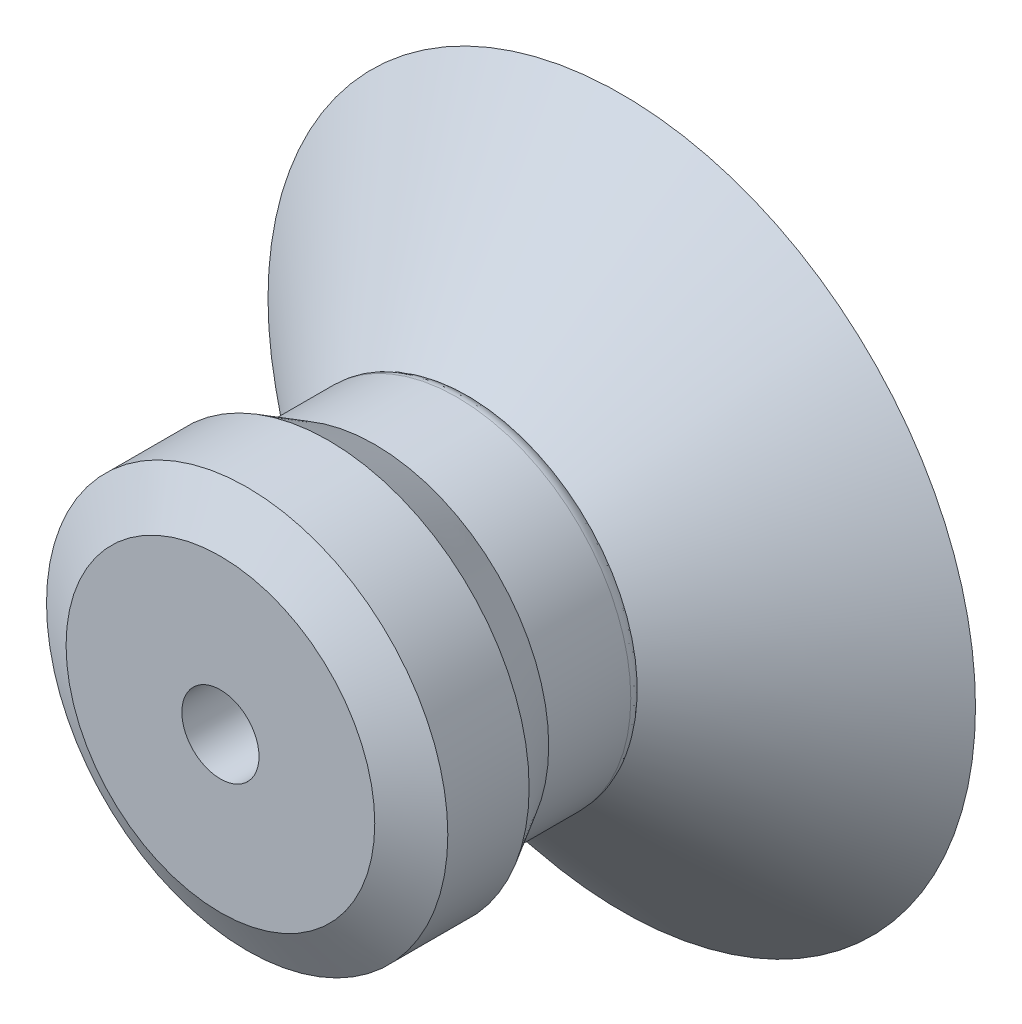
SolidWorks part; units mm, degrees
ref_plane "Front Plane" through (0, 0, 0) normal (0, 0, 1) x (1, 0, 0)
ref_plane "Top Plane" through (0, 0, 0) normal (0, 1, 0) x (1, 0, 0)
ref_plane "Right Plane" through (0, 0, 0) normal (1, 0, 0) x (0, 0, -1)
sketch "Sketch56" plane through (0, 0, -24.5) normal (0, 0, -1) x (-1, 0, 0)
  circle A0 centre (0, 0) radius 6.5
  dimension "D1" = 13
extrude "Boss-Extrude10" add sketch "Sketch56" along normal blind 5
chamfer "Chamfer1" distance 1.5 angle 30 1 edges at (-6.5, 0, -24.5) first distance on face at (-6.5, 0, -24.5)
chamfer "Chamfer2" distance 1.5 angle 30 1 edges at (-6.5, 0, -29.5) first distance on face at (-6.5, 0, -25.366)
sketch "Sketch59" plane through (0, 0, -29.5) normal (0, 0, -1) x (-1, 0, 0)
  circle A0 centre (0, 0) radius 5.634
  circle A1 centre (0, 0) radius 5.634 construction
  dimension "D1" = 0
extrude "Boss-Extrude12" add sketch "Sketch59" along normal blind 3
sketch "Sketch60" plane through (0, 0, -32.5) normal (0, 0, -1) x (-1, 0, 0)
  circle A0 centre (0, 0) radius 5.5
  dimension "D1" = 11
extrude "Boss-Extrude13" add sketch "Sketch60" along normal blind 5 draft 50 draft outward yes
sketch "Sketch62" plane through (0, 0, 0) normal (1, 0, 0) x (0, 0, -1)
  line L0 (32.5, 0) -> (37.5, 0)
  line L1 (32.5, -5.634) -> (32.5, 5.634) construction
  line L2 (37.5, -11.4588) -> (37.5, 11.4588) construction
  line L5 (37.5, 10.9221) -> (37.5, 0)
  line L7 (32.5, 0) -> (37.5, 10.9221)
  line L8 (37.5, 10.9221) -> (37.5, 0)
  dimension "D1" = 10.9221
revolve "Cut-Revolve2" cut sketch "Sketch62" angle 360 about L0 region at (0, 3.6407, -35.8333)
sketch "Sketch64" plane through (0, 0, -24.5) normal (0, 0, 1) x (1, 0, 0)
  circle A0 centre (0, 0) radius 1.25
  dimension "D1" = 2.5
extrude "Cut-Extrude3" cut sketch "Sketch64" against normal blind 53
fillet "Fillet3" radius 0.5 1 edges at (-5.634, 0, -32.5)
scale "Scale1" scale about centroid uniform scaling yes scale factor 5
